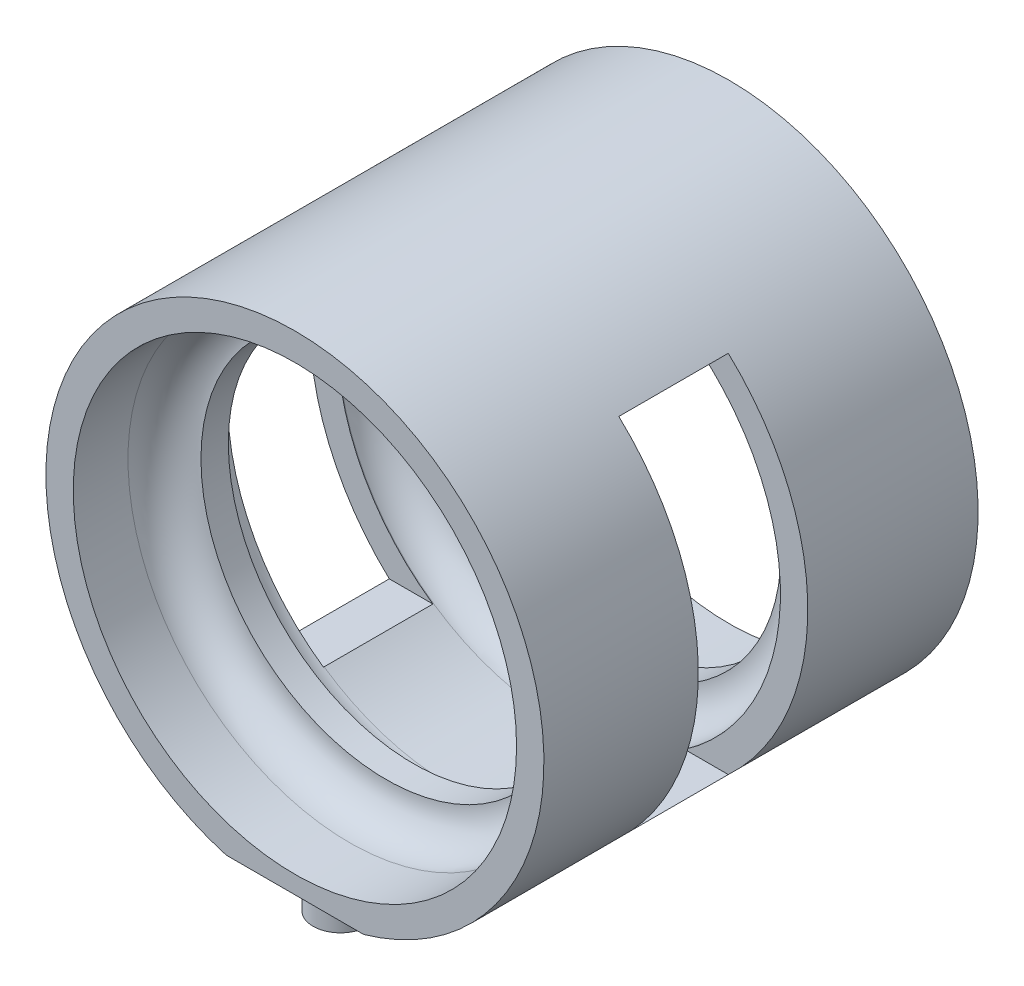
SolidWorks part; units mm, degrees
ref_plane "Front Plane" through (0, 0, 0) normal (0, 0, 1) x (1, 0, 0)
ref_plane "Top Plane" through (0, 0, 0) normal (0, 1, 0) x (1, 0, 0)
ref_plane "Right Plane" through (0, 0, 0) normal (1, 0, 0) x (0, 0, -1)
sketch "Sketch1" plane through (0, 0, 0) normal (0, 0, 1) x (1, 0, 0)
  line L0 (-3.7667, -13.12) -> (3.7667, -13.12)
  line L1 (0, -55) -> (0, 55) construction
  line L2 (0, -13.65) -> (6.7961, -13.65) construction
  circle A0 centre (0, 0) radius 12.15
  circle A1 centre (0, 0) radius 13.65
  point P6 (0, -13.12)
  dimension "D1" = 24.3
  dimension "D2" = 27.3
  dimension "D3" = 0.53
extrude "Boss-Extrude1" add sketch "Sketch1" along normal blind 23.8 contours L0 A1 A0 region at (-7.983, 10.5973, 0)
sketch "Sketch2" plane through (0, 0, 23.8) normal (0, 0, 1) x (1, 0, 0)
  circle A1 centre (0, 0) radius 12.15
  circle A2 centre (0, 0) radius 10.15
  circle A3 centre (0, 0) radius 10.15
  dimension "D1" = 2
extrude "Boss-Extrude2" add sketch "Sketch2" against normal blind 1.5 from offset 5 offset against normal yes
extrude "Boss-Extrude3" add sketch "Sketch2<2>" along normal blind 1.5 from offset 18 offset against normal yes
sketch "Sketch2<2>" plane through (0, 0, 23.8) normal (0, 0, 1) x (1, 0, 0) same geometry as "Sketch2"
sketch "Sketch4" plane through (0, 0, 0) normal (1, 0, 0) x (0, 0, -1)
  line L0 (13.09, 0) -> (-13.09, 0) construction
  line L1 (-15.3358, -10) -> (-9.3358, -10)
  line L2 (-15.3358, -10) -> (-15.3358, 10)
  line L3 (-15.3358, 10) -> (-9.3358, 10)
  line L4 (-9.3358, -10) -> (-9.3358, 10)
  line L5 (-15.3358, -10) -> (-9.3358, 10) construction
  line L6 (-15.3358, 10) -> (-9.3358, -10) construction
  point P0 (-12.3358, 0)
  dimension "D1" = 20
  dimension "D2" = 6
extrude "Cut-Extrude1" cut sketch "Sketch4" against normal through all both and the other way through all
sketch "Sketch5" plane through (0, -13.12, 0) normal (0, -1, 0) x (1, 0, 0)
  line L0 (0, 23.8) -> (0, 0) construction
  line L1 (-3.7667, 23.8) -> (3.7667, 23.8) construction
  line L2 (0, 21.3) -> (0, 2.5) construction
  circle A0 centre (0, 21.3) radius 1.5
  circle A1 centre (0, 2.5) radius 1.5
  point P7 (0, 11.9)
  point P8 (0, 11.9)
  dimension "D2" = 3
  dimension "D3" = 3
  dimension "D1" = 18.8
extrude "Boss-Extrude4" add sketch "Sketch5" along normal blind 2
fillet "Fillet1" radius 2 4 edges at (12.15, 0, 5.8) (12.15, 0, 7.3) (12.15, 0, 17.3) (12.15, 0, 18.8)
